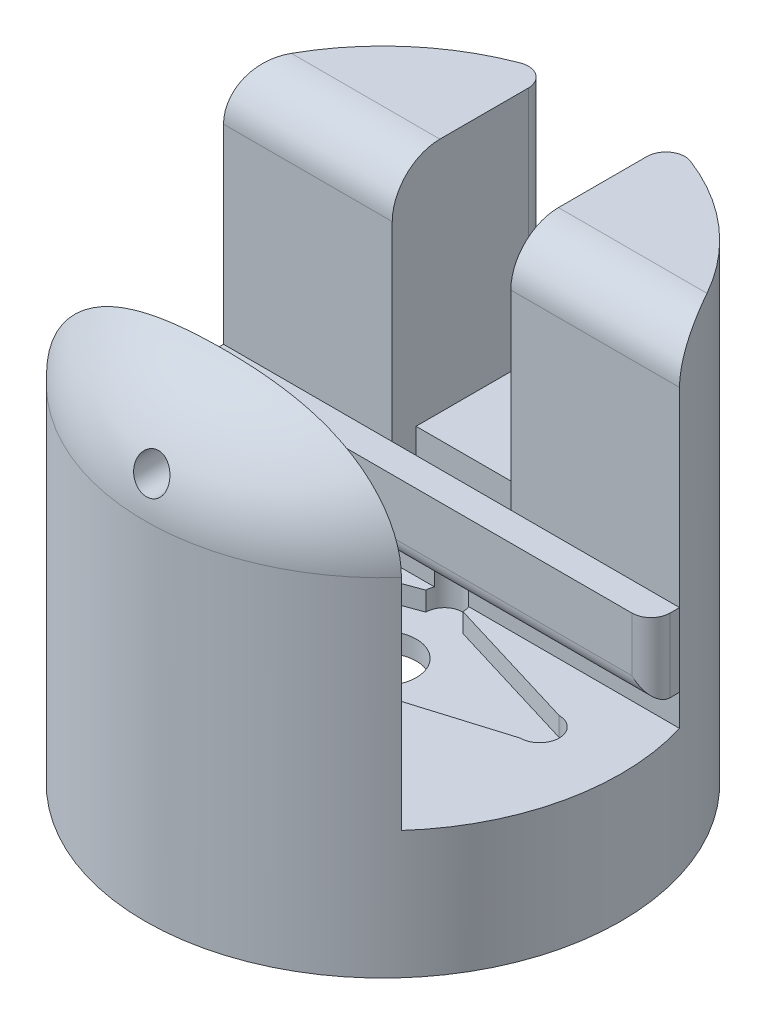
SolidWorks part; units mm, degrees
note: The reader was unsure of these and kept them because the rebuilt part matched: shared geometry of "Sketch5<3>", "Sketch6<4>", "Sketch6<5>".
ref_plane "Front Plane" through (0, 0, 0) normal (0, 0, 1) x (1, 0, 0)
ref_plane "Top Plane" through (0, 0, 0) normal (0, 1, 0) x (1, 0, 0)
ref_plane "Right Plane" through (0, 0, 0) normal (1, 0, 0) x (0, 0, -1)
sketch "Sketch1" plane through (0, 0, 0) normal (0, 1, 0) x (1, 0, 0)
  circle A0 centre (0, 0) radius 25
  circle A1 centre (0, 0) radius 22.5
  dimension "D1" = 50
  dimension "D2" = 45
extrude "Boss-Extrude1" add sketch "Sketch1" along normal blind 9.4
sketch "Sketch2" plane through (0, 9.4, 0) normal (0, 1, 0) x (1, 0, 0)
  circle A0 centre (0, 0) radius 25
extrude "Boss-Extrude2" add sketch "Sketch2" along normal blind 40
sketch "Sketch3" plane through (0, 49.4, 0) normal (0, 1, 0) x (1, 0, 0)
  line L1 (-30.3806, 7.199) -> (25, 7.199)
  line L2 (-30.3806, 7.199) -> (-30.3806, -26.7992)
  line L3 (-30.3806, -26.7992) -> (25, -26.7992)
  line L4 (25, 7.199) -> (25, -26.7992)
extrude "Cut-Extrude1" cut sketch "Sketch3" against normal blind 36
sketch "Sketch4" plane through (0, 9.4, 0) normal (0, -1, 0) x (1, 0, 0)
  circle A0 centre (0, 0) radius 3.5
  dimension "D1" = 7
extrude "Cut-Extrude2" cut sketch "Sketch4" against normal blind 36
sketch "Sketch5" plane through (0, 13.4, 0) normal (0, 1, 0) x (1, 0, 0)
  line L0 (-14.05, 2.05) -> (-1.95, 6.45)
  line L1 (-14.05, -2.05) -> (-1.95, -6.45)
  line L2 (1.95, -6.45) -> (16.45, -2.05)
  line L3 (1.95, 6.45) -> (16.45, 2.05)
  circle A0 centre (16.45, 0) radius 2.05
  circle A1 centre (-14.05, 0) radius 2.05
  circle A2 centre (0, -6.45) radius 1.95
  circle A3 centre (0, 6.45) radius 1.95
  circle A4 centre (0, 0) radius 3.5 construction
  circle M1 centre (0, 0) radius 3.5
  line M3 (23.9411, 7.199) -> (-23.9411, 7.199)
  dimension "D1" = 4.1
  dimension "D2" = 4.1
  dimension "D3" = 3.9
  dimension "D4" = 3.9
  dimension "D7" = 6.45
  dimension "D5" = 14.05
  dimension "D6" = 16.45
  dimension "D8" = 6.45
extrude "Cut-Extrude3" cut sketch "Sketch5" against normal blind 2 contours A3 L0 A1 L1 A2 L2 A0 L3 M1 | A3 M3 | A1 | A0 | A2
extrude "Cut-Extrude4" cut sketch "Sketch5<3>" along normal blind 2 contours A3
sketch "Sketch5<3>" plane through (0, 13.4, 0) normal (0, 1, 0) x (1, 0, 0) same geometry as "Sketch5"
sketch "Sketch6" plane through (0, 0, -7.199) normal (0, 0, 1) x (1, 0, 0)
  line L0 (0, 0) -> (0, 49.4) construction
  line L1 (23.9411, 49.4) -> (-23.9411, 49.4) construction
  line L3 (-6.225, 24.5376) -> (6.225, 24.5376)
  line L4 (-6.225, 24.5376) -> (-6.225, 47.0876)
  line L5 (-6.225, 47.0876) -> (6.225, 47.0876)
  line L6 (6.225, 24.5376) -> (6.225, 47.0876)
  line L7 (-6.225, 24.5376) -> (6.225, 47.0876) construction
  line L8 (-6.225, 47.0876) -> (6.225, 24.5376) construction
  line L9 (-6.225, 24.5376) -> (6.225, 24.5376)
  line L10 (-6.225, 24.5376) -> (-6.225, 19.6876)
  line L11 (-6.225, 19.6876) -> (6.225, 19.6876)
  line L12 (6.225, 24.5376) -> (6.225, 19.6876)
  line L13 (-6.225, 47.0876) -> (6.225, 47.0876)
  line L14 (-6.225, 47.0876) -> (-6.225, 50.3833)
  line L15 (-6.225, 50.3833) -> (6.225, 50.3833)
  line L16 (6.225, 47.0876) -> (6.225, 50.3833)
  point P5 (0, 35.8126)
  line M4 (23.9411, 49.4) -> (-23.9411, 49.4)
  dimension "D1" = 22.55
  dimension "D2" = 12.45
  dimension "D3" = 4.85
extrude "Cut-Extrude5" cut sketch "Sketch6" against normal blind 42 contours L3 L6 L5 L4
extrude "Cut-Extrude6" cut sketch "Sketch6<4>" against normal blind 2.5 contours L12 L3 L10 L11
sketch "Sketch6<4>" plane through (0, 0, -7.199) normal (0, 0, 1) x (1, 0, 0) same geometry as "Sketch6"
extrude "Cut-Extrude7" cut sketch "Sketch6<5>" against normal blind 28.5 contours L5 L16 L14 M4
sketch "Sketch6<5>" plane through (0, 0, -7.199) normal (0, 0, 1) x (1, 0, 0) same geometry as "Sketch6"
sketch "Sketch7" plane through (0, 0, -7.199) normal (0, 0, 1) x (1, 0, 0)
  line L0 (-23.9411, 13.4) -> (-23.9411, 49.4) construction
  line L1 (-23.9411, 19.6876) -> (23.9411, 19.6876)
  line L2 (-23.9411, 19.6876) -> (-23.9411, 16.6876)
  line L3 (-23.9411, 16.6876) -> (23.9411, 16.6876)
  line L4 (23.9411, 19.6876) -> (23.9411, 16.6876)
  line L5 (23.9411, 49.4) -> (23.9411, 13.4) construction
  line L6 (-6.225, 19.6876) -> (6.225, 19.6876) construction
  dimension "D1" = 3
extrude "Boss-Extrude3" add sketch "Sketch7" along normal blind 3
sketch "Sketch8" plane through (0, 19.6876, 0) normal (0, 1, 0) x (1, 0, 0)
  line L0 (23.9411, 4.199) -> (-23.9411, 4.199) construction
  line L1 (-23.9411, 7.199) -> (23.9411, 7.199)
  line L2 (-23.9411, 7.199) -> (-23.9411, 4.199)
  line L3 (-23.9411, 4.199) -> (23.9411, 4.199)
  line L4 (23.9411, 7.199) -> (23.9411, 4.199)
extrude "Boss-Extrude4" add sketch "Sketch8" along normal blind 4.7
fillet "Fillet1" radius 5 2 edges at (15.083, 49.4, -7.199) (-15.083, 49.4, -7.199)
fillet "Fillet2" radius 2 2 edges at (6.225, 36.9688, -24.2126) (-6.225, 36.9688, -24.2126)
fillet "Fillet3" radius 2 3 edges at (0, 16.6876, -4.199) (23.9411, 20.5376, -4.199) (-23.9411, 20.5376, -4.199)
sketch "Sketch9" plane through (0, 13.4, 0) normal (0, 1, 0) x (1, 0, 0)
  line L0 (-18.6197, -16.6825) -> (18.6197, -16.6825)
  circle A0 centre (0, 0) radius 25
  arc A1 (-23.9411, 7.199) -> (23.9411, 7.199) centre (0, 0) ccw construction
  arc M12 (-23.9411, 7.199) -> (23.9411, 7.199) centre (0, 0) ccw
extrude "Boss-Extrude5" add sketch "Sketch9" along normal blind 35 contours L0 M12
fillet "Fillet4" radius 12 2 edges at (0, 48.4, 16.6825) (0, 48.4, 25)
sketch "Sketch10" plane through (0, 0, 16.6825) normal (0, 0, -1) x (-1, 0, 0)
  line L0 (0, 0) -> (0, 40.29) construction
  circle A0 centre (0, 40.29) radius 1.8
  dimension "D2" = 3.6
  dimension "D1" = 40.29
extrude "Cut-Extrude8" cut sketch "Sketch10" against normal blind 36
